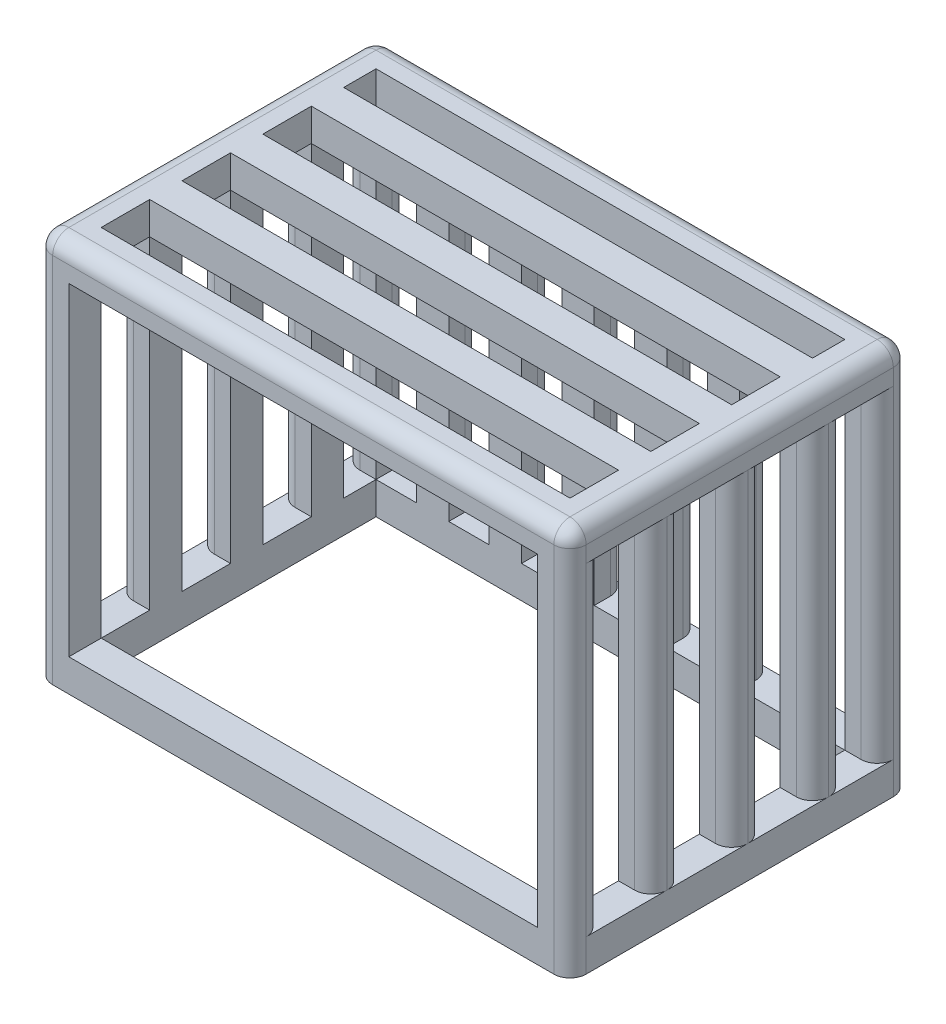
SolidWorks part; units mm, degrees
ref_plane "Front" through (0, 0, 0) normal (0, 0, 1) x (1, 0, 0)
ref_plane "Top" through (0, 0, 0) normal (0, 1, 0) x (1, 0, 0)
ref_plane "Right" through (0, 0, 0) normal (1, 0, 0) x (0, 0, -1)
sketch "草图1" plane through (0, 0, 0) normal (0, 1, 0) x (1, 0, 0)
  line L0 (2, -19) -> (31, -19)
  line L1 (0, 0) -> (33, 0)
  line L2 (0, 0) -> (0, -21)
  line L3 (0, -21) -> (33, -21)
  line L4 (33, 0) -> (33, -21)
  line L5 (31, -2) -> (31, -19)
  line L6 (2, -2) -> (31, -2)
  line L7 (2, -2) -> (2, -19)
  dimension "D1" = 33
  dimension "D2" = 21
  dimension "D3" = 2
extrude "凸台-拉伸1" add sketch "草图1" along normal blind 2
sketch "草图2" plane through (0, 2, 0) normal (0, 1, 0) x (1, 0, 0)
  line L0 (0, -14) -> (2, -14)
  line L1 (0, -21) -> (2, -21)
  line L2 (0, -21) -> (0, -19)
  line L3 (0, -19) -> (2, -19)
  line L4 (2, -21) -> (2, -19)
  line L5 (0, 0) -> (2, 0)
  line L6 (0, 0) -> (0, -2)
  line L7 (0, -2) -> (2, -2)
  line L8 (2, 0) -> (2, -2)
  line L9 (33, 0) -> (31, 0)
  line L10 (33, 0) -> (33, -2)
  line L11 (33, -2) -> (31, -2)
  line L12 (31, 0) -> (31, -2)
  line L13 (33, -21) -> (31, -21)
  line L14 (33, -21) -> (33, -19)
  line L15 (33, -19) -> (31, -19)
  line L16 (31, -21) -> (31, -19)
  line L17 (2, -16) -> (2, -14)
  line L18 (0, -16) -> (2, -16)
  line L19 (0, -16) -> (0, -14)
  line L20 (33, -16) -> (31, -16)
  line L21 (31, -16) -> (31, -14)
  line L22 (33, -14) -> (31, -14)
  line L23 (33, -16) -> (33, -14)
  line L24 (0, -9) -> (2, -9)
  line L25 (2, -11) -> (2, -9)
  line L26 (0, -11) -> (2, -11)
  line L27 (0, -11) -> (0, -9)
  line L28 (33, -11) -> (31, -11)
  line L29 (31, -11) -> (31, -9)
  line L30 (33, -9) -> (31, -9)
  line L31 (33, -11) -> (33, -9)
  line L32 (0, -4) -> (2, -4)
  line L33 (2, -6) -> (2, -4)
  line L34 (0, -6) -> (2, -6)
  line L35 (0, -6) -> (0, -4)
  line L36 (33, -6) -> (31, -6)
  line L37 (31, -6) -> (31, -4)
  line L38 (33, -4) -> (31, -4)
  line L39 (33, -6) -> (33, -4)
  line L40 (4.5, -2) -> (6.5, -2)
  line L41 (4.5, 0) -> (4.5, -2)
  line L42 (4.5, 0) -> (6.5, 0)
  line L43 (6.5, 0) -> (6.5, -2)
  line L44 (9, -2) -> (11, -2)
  line L45 (9, 0) -> (9, -2)
  line L46 (9, 0) -> (11, 0)
  line L47 (11, 0) -> (11, -2)
  line L48 (13.5, -2) -> (15.5, -2)
  line L49 (13.5, 0) -> (13.5, -2)
  line L50 (13.5, 0) -> (15.5, 0)
  line L51 (15.5, 0) -> (15.5, -2)
  line L52 (18, -2) -> (20, -2)
  line L53 (18, 0) -> (18, -2)
  line L54 (18, 0) -> (20, 0)
  line L55 (20, 0) -> (20, -2)
  line L56 (22.5, -2) -> (24.5, -2)
  line L57 (22.5, 0) -> (22.5, -2)
  line L58 (22.5, 0) -> (24.5, 0)
  line L59 (24.5, 0) -> (24.5, -2)
  line L60 (27, -2) -> (29, -2)
  line L61 (27, 0) -> (27, -2)
  line L62 (27, 0) -> (29, 0)
  line L63 (29, 0) -> (29, -2)
  dimension "D1" = 4
  dimension "D2" = 7
extrude "凸台-拉伸2" add sketch "草图2" along normal blind 20
sketch "草图3" plane through (0, 22, 0) normal (0, 1, 0) x (1, 0, 0)
  line L3 (0, -21) -> (2, -21)
  line L4 (0, -21) -> (0, 0)
  line L6 (0, 0) -> (2, 0)
  line L7 (2, -21) -> (2, 0)
  line L8 (2, 0) -> (33, 0)
  line L9 (2, 0) -> (2, -2)
  line L11 (2, -2) -> (33, -2)
  line L12 (33, 0) -> (33, -2)
  line L13 (33, -2) -> (31, -2)
  line L14 (33, -2) -> (33, -21)
  line L15 (33, -21) -> (31, -21)
  line L16 (31, -2) -> (31, -21)
  line L17 (2, -6) -> (31, -6)
  line L18 (2, -6) -> (2, -4)
  line L19 (2, -4) -> (31, -4)
  line L20 (31, -6) -> (31, -4)
  line L21 (31, -9) -> (2, -9)
  line L22 (31, -9) -> (31, -11)
  line L23 (31, -11) -> (2, -11)
  line L24 (2, -9) -> (2, -11)
  line L25 (2, -14) -> (31, -14)
  line L26 (2, -14) -> (2, -16)
  line L27 (2, -16) -> (31, -16)
  line L28 (31, -14) -> (31, -16)
  line L29 (31, -19) -> (2, -19)
  line L30 (31, -19) -> (31, -21)
  line L31 (31, -21) -> (2, -21)
  line L32 (2, -19) -> (2, -21)
extrude "凸台-拉伸6" add sketch "草图3" along normal blind 2
fillet "圆角2" radius 1 38 edges at (33, 12, 19) (33, 12, 16) (33, 12, 14) (33, 12, 11) (33, 12, 9) (33, 12, 6) (33, 12, 4) (33, 12, 2) (0, 12, 19) (0, 12, 16) (0, 12, 14) (0, 12, 11) (0, 12, 9) (0, 12, 6) (0, 12, 4) (0, 12, 2) (2, 12, 0) (4.5, 12, 0) (6.5, 12, 0) (9, 12, 0) (11, 12, 0) (13.5, 12, 0) (15.5, 12, 0) (18, 12, 0) (20, 12, 0) (22.5, 12, 0) (24.5, 12, 0) (27, 12, 0) (29, 12, 0) (31, 12, 0) (33, 24, 10.5) (33, 12, 0) (16.5, 24, 0) (0, 12, 0) (0, 12, 21) (0, 24, 10.5) (16.5, 24, 21) (33, 12, 21)
